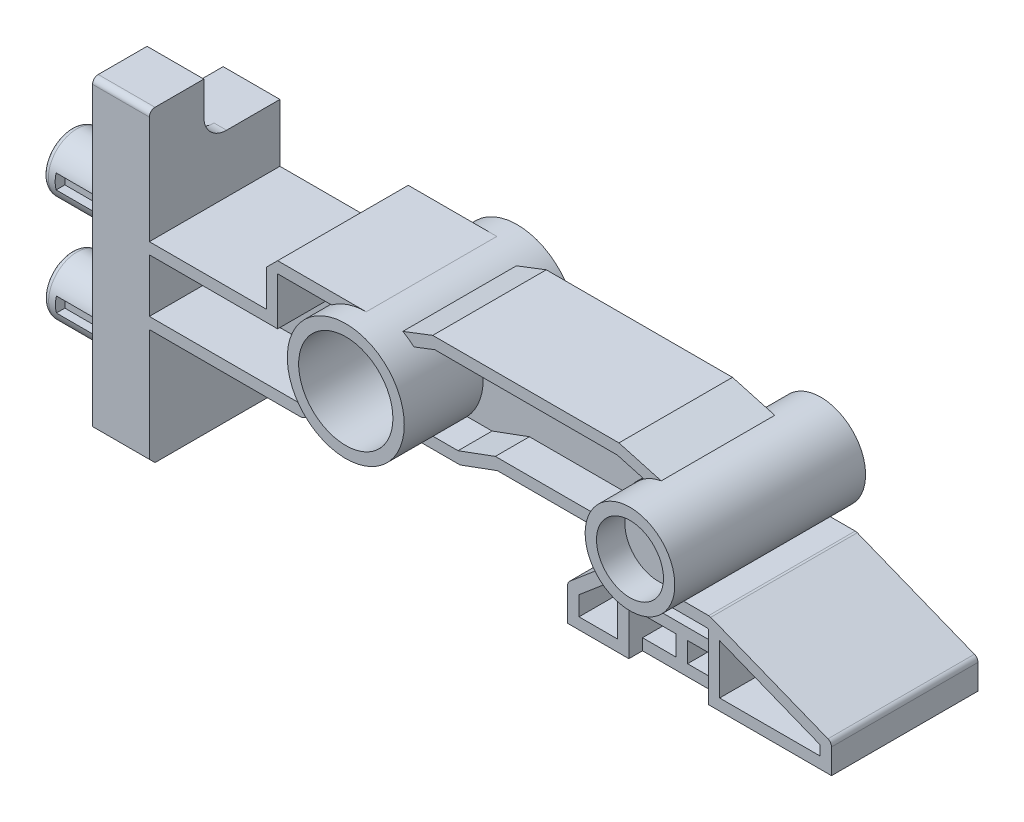
SolidWorks part; units mm, degrees
material "ABS"
ref_plane "Front Plane" through (0, 0, 0) normal (0, 0, 1) x (1, 0, 0)
ref_plane "Top Plane" through (0, 0, 0) normal (0, 1, 0) x (1, 0, 0)
ref_plane "Right Plane" through (0, 0, 0) normal (1, 0, 0) x (0, 0, -1)
sketch "Sketch1" plane through (0, 0, 0) normal (0, 0, 1) x (1, 0, 0)
  circle A0 centre (0, 0) radius 5.15
  circle A1 centre (0, 0) radius 4.15
  dimension "D1" = 10.3
  dimension "D2" = 1
extrude "Boss-Extrude1" add sketch "Sketch1" along normal blind 15.1
ref_plane "Plane1" through (0, 0, 1.8) normal (0, 0, -1) x (-1, 0, 0)
sketch "Sketch2" plane through (0, 0, 1.8) normal (0, 0, -1) x (-1, 0, 0)
  line L0 (0, 5.15) -> (8.8, 5.15)
  line L1 (8.8, 5.15) -> (8.8, 0.95)
  line L2 (8.8, 0.95) -> (19.1, 0.95)
  line L3 (2.7907, -4.3283) -> (5.6739, -5.7513)
  line L4 (5.6739, -5.7513) -> (19.1, -5.7513)
  line L6 (19.1, -5.7513) -> (19.1, -16.1513)
  line L7 (19.1, 0.95) -> (19.1, 10.95)
  line L8 (19.1, 10.95) -> (24.1, 10.95)
  line L9 (19.1, -16.1513) -> (24.1, -16.1513)
  line L10 (24.1, -16.1513) -> (24.1, 10.95)
  circle A0 centre (0, 0) radius 5.15 construction
  arc A1 (2.7907, -4.3283) -> (0, 5.15) centre (0, 0) ccw
  dimension "D1" = 8.8
  dimension "D2" = 4.2
  dimension "D3" = 10.3
  dimension "D4" = 10.4
  dimension "D5" = 10
  dimension "D6" = 5
extrude "Boss-Extrude2" add sketch "Sketch2" against normal blind 11.5
sketch "Sketch3" plane through (0, 0, 1.8) normal (0, 0, -1) x (-1, 0, 0)
  line L0 (-2.4711, 4.5184) -> (-5.1046, 5.5315)
  line L2 (-5.1046, 5.5315) -> (-21.5046, 5.5315)
  line L3 (-2.4138, -4.5493) -> (-6.1138, -4.5493)
  line L4 (-6.1138, -4.5493) -> (-9.3984, -3.3405)
  line L5 (-9.3984, -3.3405) -> (-21.5311, -3.3405)
  line L6 (-21.5046, 5.5315) -> (-25.2287, 4.4975)
  line L7 (-21.5311, -3.3405) -> (-25.9262, -3.3405)
  circle A0 centre (0, 0) radius 5.15 construction
  arc A1 (-25.9262, -3.3405) -> (-25.2287, 4.4975) centre (-25.9262, 0.6095) ccw
  arc A2 (-2.4711, 4.5184) -> (-2.4138, -4.5493) centre (0, 0) ccw
  dimension "D5" = 7.9
  dimension "D2" = 16.4
  dimension "D3" = 3.7
  dimension "D4" = 3.5
ref_plane "Plane2" through (0, 0, -0.8) normal (0, 0, -1) x (-1, 0, 0)
ref_plane "Plane3" through (0, 0, 2.55) normal (0, 0, -1) x (-1, 0, 0)
sketch "Sketch5" plane through (0, 0, 2.55) normal (0, 0, -1) x (-1, 0, 0)
  line L0 (-2.4711, 4.5184) -> (-5.1046, 5.5315)
  line L1 (-5.1046, 5.5315) -> (-21.5046, 5.5315)
  line L2 (-21.5046, 5.5315) -> (-25.2287, 4.4975)
  line L3 (-25.9262, -3.3405) -> (-21.5311, -3.3405)
  line L4 (-21.5311, -3.3405) -> (-9.3984, -3.3405)
  line L5 (-9.3984, -3.3405) -> (-6.1138, -4.5493)
  line L6 (-6.1138, -4.5493) -> (-2.4138, -4.5493)
  arc A0 (-2.4711, 4.5184) -> (-2.4138, -4.5493) centre (0, 0) ccw
  arc A1 (-25.9262, -3.3405) -> (-25.2287, 4.4975) centre (-25.9262, 0.6095) ccw
extrude "Boss-Extrude5" add sketch "Sketch5" against normal blind 10
sketch "Sketch6" plane through (0, 0, -0.8) normal (0, 0, -1) x (-1, 0, 0)
  circle A0 centre (-25.9262, 0.6095) radius 3.95
extrude "Boss-Extrude6" add sketch "Sketch6" against normal blind 16.8
sketch "Sketch7" plane through (-24.1, 0, 0) normal (-1, 0, 0) x (0, 0, 1)
  line L1 (13.3, 10.95) -> (1.8, 10.95) construction
  line L2 (8.5, 10.95) -> (8.5, 6.05)
  line L3 (8.5, 6.05) -> (1.8, 6.05)
  line L4 (1.8, -16.1513) -> (1.8, 10.95) construction
  line L5 (1.8, 6.05) -> (1.8, 10.95)
  line L6 (1.8, 10.95) -> (8.5, 10.95)
  dimension "D2" = 4.9
extrude "Cut-Extrude1" cut sketch "Sketch7" against normal blind 16.8
sketch "Sketch8" plane through (-24.1, 0, 0) normal (-1, 0, 0) x (0, 0, 1)
  line L0 (7.5573, -15.7) -> (7.6164, 7.3801) construction
  line L2 (13.3, -16.1513) -> (1.8, -16.1513) construction
  line L3 (1.8, 6.05) -> (8.5, 6.05) construction
  circle A1 centre (7.5687, -11.2513) radius 2.5
  circle A2 centre (7.5928, -1.85) radius 2.5
  dimension "D1" = 5
  dimension "D3" = 5
  dimension "D4" = 7.9
  dimension "D2" = 4.9
extrude "Boss-Extrude7" add sketch "Sketch8" along normal blind 7.6
sketch "Sketch9" plane through (0, 0, -0.8) normal (0, 0, -1) x (-1, 0, 0)
  circle A0 centre (-25.9262, 0.6095) radius 2.95
  circle A1 centre (-25.9262, 0.6095) radius 3.95 construction
  dimension "D1" = 1
extrude "Cut-Extrude2" cut sketch "Sketch9" against normal blind 13.4
sketch "Sketch10" plane through (0, 0, 16) normal (0, 0, 1) x (1, 0, 0)
  circle A0 centre (25.9262, 0.6095) radius 2.95
  circle A1 centre (25.9262, 0.6095) radius 3.95 construction
  dimension "D1" = 1
extrude "Cut-Extrude3" cut sketch "Sketch10" against normal blind 2.5
ref_plane "Plane5" through (0, 0, 1) normal (0, 0, -1) x (-1, 0, 0)
sketch "Sketch11" plane through (0, 0, 1) normal (0, 0, -1) x (-1, 0, 0)
  line L2 (-33.12, -3.243) -> (-41.5746, -6.6092)
  line L3 (-41.5746, -6.6092) -> (-41.5746, -9.1405)
  line L4 (-21.9682, -2.9208) -> (-18.3416, -5.9852)
  line L5 (-18.3416, -5.9852) -> (-18.3416, -9.1405)
  line L6 (-18.3416, -9.1405) -> (-41.5746, -9.1405)
  line L7 (-33.12, -3.243) -> (-30.8531, -2.3405)
  line L8 (-30.8531, -2.3405) -> (-28.553, -2.3405)
  line L9 (-21.9682, -2.9208) -> (-22.655, -2.3405)
  line L10 (-23.2994, -2.3405) -> (-22.655, -2.3405)
  line L11 (-25.9262, -3.3405) -> (-9.3984, -3.3405) construction
  arc A1 (-28.553, -2.3405) -> (-23.2994, -2.3405) centre (-25.9262, 0.6095) ccw
  dimension "D1" = 6.8
  dimension "D2" = 23.2329
  dimension "D3" = 1
extrude "Boss-Extrude14" add sketch "Sketch11" against normal blind 12.9
sketch "Sketch13" plane through (0, 0, 8.5) normal (0, 0, -1) x (-1, 0, 0)
  line L1 (20.2, 9.85) -> (23, 9.85)
  line L2 (20.2, 9.85) -> (20.2, 6.05)
  line L3 (20.2, 6.05) -> (23, 6.05)
  line L4 (23, 9.85) -> (23, 6.05)
  line L5 (19.1, 6.05) -> (24.1, 6.05) construction
  line L6 (19.1, 10.95) -> (24.1, 10.95) construction
  line L7 (19.1, 10.95) -> (19.1, 6.05) construction
  line L8 (24.1, 6.05) -> (24.1, 10.95) construction
  dimension "D1" = 1.1
  dimension "D2" = 1.1
  dimension "D3" = 1.1
extrude "Cut-Extrude4" cut sketch "Sketch13" against normal blind 3.6
sketch "Sketch14" plane through (0, 0, 1.8) normal (0, 0, -1) x (-1, 0, 0)
  line L0 (20.2, 6.05) -> (23, 6.05) construction
  line L1 (20.1, 5.05) -> (23.1, 5.05)
  line L2 (20.1, 5.05) -> (20.1, -1.55)
  line L3 (20.1, -1.55) -> (23.1, -1.55)
  line L4 (23.1, 5.05) -> (23.1, -1.55)
  line L5 (20.1, -2.55) -> (23.1, -2.55)
  line L6 (20.1, -2.55) -> (20.1, -10.65)
  line L7 (20.1, -10.65) -> (23.1, -10.65)
  line L8 (23.1, -2.55) -> (23.1, -10.65)
  line L9 (20.1, -11.65) -> (23.1, -11.65)
  line L10 (20.1, -11.65) -> (20.1, -15.1513)
  line L11 (20.1, -15.1513) -> (23.1, -15.1513)
  line L12 (23.1, -11.65) -> (23.1, -15.1513)
  line L13 (24.1, -16.1513) -> (24.1, 6.05) construction
  line L14 (21.6, 6.05) -> (21.6, -16.1513) construction
  line L15 (19.1, -16.1513) -> (24.1, -16.1513) construction
  line L18 (19.1, 6.05) -> (19.1, 0.95) construction
  point P18 (21.6, 5.05)
  dimension "D1" = 1
  dimension "D2" = 6.6
  dimension "D3" = 1
  dimension "D4" = 1
  dimension "D5" = 8.1
  dimension "D6" = 1
  dimension "D7" = 1
  dimension "D8" = 1
extrude "Cut-Extrude5" cut sketch "Sketch14" against normal blind 10.2
sketch "Sketch15" plane through (-24.1, 0, 0) normal (-1, 0, 0) x (0, 0, 1)
  line L0 (7.5928, -1.85) -> (7.5928, -11.2514) construction
  line L1 (10.0928, -1.85) -> (5.0928, -1.85) construction
  line L2 (4.7322, -1.2) -> (5.9454, -1.2)
  line L3 (4.7322, -1.2) -> (4.7322, -2.5)
  line L4 (4.7322, -2.5) -> (5.9454, -2.5)
  line L5 (5.9454, -1.2) -> (5.9454, -2.5)
  line L6 (10.4534, -2.5) -> (9.2402, -2.5)
  line L7 (9.2402, -1.2) -> (9.2402, -2.5)
  line L8 (10.4534, -1.2) -> (9.2402, -1.2)
  line L9 (10.4534, -1.2) -> (10.4534, -2.5)
  line L10 (4.7322, -6.55) -> (10.0928, -6.55) construction
  line L11 (10.4534, -11.9) -> (10.4534, -10.6)
  line L12 (10.4534, -11.9) -> (9.2402, -11.9)
  line L13 (9.2402, -11.9) -> (9.2402, -10.6)
  line L14 (10.4534, -10.6) -> (9.2402, -10.6)
  line L15 (4.7322, -10.6) -> (5.9454, -10.6)
  line L16 (5.9454, -11.9) -> (5.9454, -10.6)
  line L17 (4.7322, -11.9) -> (5.9454, -11.9)
  line L18 (4.7322, -11.9) -> (4.7322, -10.6)
  circle A2 centre (7.5928, -1.85) radius 2.5 construction
  circle A3 centre (7.5928, -1.85) radius 2.5 construction
  point P2 (5.9454, -1.85)
  dimension "D4" = 4.7
  dimension "D1" = 1.3
  dimension "D2" = 1.6474
  dimension "D3" = 0.65
extrude "Cut-Extrude6" cut sketch "Sketch15" along normal blind 6.5
ref_plane "Plane7" through (0, 0, 7.55) normal (0, 0, 1) x (1, 0, 0)
sketch "Sketch16" plane through (0, 0, 1.8) normal (0, 0, -1) x (-1, 0, 0)
  line L0 (7.8, 4.15) -> (7.8, -0.05)
  line L1 (7.8, -0.05) -> (19.1, -0.05)
  line L2 (19.1, -0.05) -> (19.1, -4.7513)
  line L3 (19.1, -4.7513) -> (7.5352, -4.7513)
  line L4 (7.5352, -4.7513) -> (5.9073, -4.7513)
  line L5 (5.9073, -4.7513) -> (3.6473, -3.6359)
  line L6 (7.8, 4.15) -> (3.0496, 4.15)
  line L7 (8.8, 5.15) -> (0, 5.15) construction
  line L8 (8.8, 0.95) -> (8.8, 5.15) construction
  line L9 (19.1, 0.95) -> (8.8, 0.95) construction
  line L10 (19.1, 6.05) -> (19.1, 0.95) construction
  line L11 (5.6739, -5.7513) -> (19.1, -5.7513) construction
  line L12 (2.7907, -4.3283) -> (5.6739, -5.7513) construction
  arc A0 (3.6473, -3.6359) -> (3.0496, 4.15) centre (0, 0) ccw
  dimension "D1" = 1
  dimension "D2" = 1
  dimension "D3" = 1
  dimension "D4" = 1
  dimension "D5" = 1
extrude "Cut-Extrude7" cut sketch "Sketch16" against normal blind 4.9
sketch "Sketch17" plane through (0, 0, 2.55) normal (0, 0, -1) x (-1, 0, 0)
  line L0 (-22.655, -2.3405) -> (-9.2203, -2.3405)
  line L1 (-9.2203, -2.3405) -> (-5.9356, -3.5493)
  line L2 (-5.9356, -3.5493) -> (-3.7316, -3.5493)
  line L3 (-3.4501, 3.8235) -> (-5.2903, 4.5315)
  line L4 (-5.2903, 4.5315) -> (-21.3684, 4.5315)
  line L5 (-21.3684, 4.5315) -> (-23.6642, 3.894)
  line L6 (-21.5046, 5.5315) -> (-25.2287, 4.4975) construction
  line L7 (-5.1046, 5.5315) -> (-21.5046, 5.5315) construction
  line L8 (-2.4711, 4.5184) -> (-5.1046, 5.5315) construction
  line L9 (-21.4715, -3.3405) -> (-9.3984, -3.3405) construction
  line L10 (-9.3984, -3.3405) -> (-6.1138, -4.5493) construction
  line L11 (-6.1138, -4.5493) -> (-2.4138, -4.5493) construction
  line L12 (-22.655, -2.3405) -> (-23.2425, -2.3405)
  arc A0 (-23.2425, -2.3405) -> (-23.6642, 3.894) centre (-25.9262, 0.6095) ccw
  arc A1 (-2.4711, 4.5184) -> (-2.4138, -4.5493) centre (0, 0) ccw construction
  arc A3 (-3.4501, 3.8235) -> (-3.7316, -3.5493) centre (0, 0) ccw
  dimension "D1" = 1
  dimension "D2" = 1
  dimension "D3" = 1
  dimension "D4" = 1
  dimension "D5" = 1
extrude "Cut-Extrude8" cut sketch "Sketch17" against normal blind 4.4
sketch "Sketch18" plane through (0, 0, 2.55) normal (0, 0, -1) x (-1, 0, 0)
  line L0 (-22.655, -2.3405) -> (-21.4715, -3.3405)
  line L1 (-21.4715, -3.3405) -> (-9.3984, -3.3405)
  line L2 (-9.3984, -3.3405) -> (-6.1138, -4.5493)
  line L3 (-6.1138, -4.5493) -> (-2.4138, -4.5493)
  line L4 (-22.655, -2.3405) -> (-9.2203, -2.3405)
  line L5 (-9.2203, -2.3405) -> (-5.9356, -3.5493)
  line L6 (-5.9356, -3.5493) -> (-3.7316, -3.5493)
  arc A0 (-2.4138, -4.5493) -> (-3.7316, -3.5493) centre (0, 0) cw
extrude "Cut-Extrude9" cut sketch "Sketch18" against normal blind 1.4
sketch "Sketch19" plane through (0, 0, 1) normal (0, 0, -1) x (-1, 0, 0)
  line L0 (-40.5746, -7.2874) -> (-40.5746, -8.1405)
  line L1 (-40.5746, -8.1405) -> (-19.3416, -8.1405)
  line L2 (-19.3416, -8.1405) -> (-19.3416, -6.4494)
  line L3 (-19.3416, -6.4494) -> (-23.0209, -3.3405)
  line L4 (-23.0209, -3.3405) -> (-30.6613, -3.3405)
  line L5 (-30.6613, -3.3405) -> (-40.5746, -7.2874)
  line L6 (-30.8531, -2.3405) -> (-41.5746, -6.6092) construction
  line L7 (-41.5746, -6.6092) -> (-41.5746, -9.1405) construction
  line L8 (-41.5746, -9.1405) -> (-18.3416, -9.1405) construction
  line L9 (-18.3416, -9.1405) -> (-18.3416, -5.9852) construction
  line L10 (-18.3416, -5.9852) -> (-22.655, -2.3405) construction
  line L11 (-28.553, -2.3405) -> (-30.8531, -2.3405) construction
  line L12 (-30.7229, -3.365) -> (-30.7229, -5.3669)
  line L13 (-30.7229, -8.1405) -> (-31.7229, -8.1405)
  line L14 (-31.7229, -8.1405) -> (-31.7229, -3.7631)
  line L15 (-31.7229, -3.7631) -> (-30.7229, -3.365)
  line L16 (-23.7295, -3.3405) -> (-23.7295, -5.3669)
  line L17 (-23.7295, -8.1405) -> (-22.7295, -8.1405)
  line L18 (-22.7295, -8.1405) -> (-22.7295, -3.5867)
  line L19 (-22.7295, -3.5867) -> (-23.0209, -3.3405)
  line L20 (-23.7295, -3.3405) -> (-23.0209, -3.3405)
  line L21 (-30.7229, -5.3669) -> (-23.7295, -5.3669)
  line L23 (-23.7295, -6.3669) -> (-26.6973, -6.3669)
  line L25 (-27.6973, -6.3669) -> (-27.6973, -8.1405)
  line L26 (-27.6973, -8.1405) -> (-26.6973, -8.1405)
  line L27 (-26.6973, -8.1405) -> (-26.6973, -6.3669)
  line L29 (-30.7229, -6.3669) -> (-30.7229, -8.1405)
  line L30 (-27.6973, -6.3669) -> (-30.7229, -6.3669)
  line L31 (-23.7295, -6.3669) -> (-23.7295, -8.1405)
  dimension "D1" = 1
  dimension "D2" = 1
  dimension "D3" = 1
  dimension "D4" = 1
  dimension "D5" = 1
  dimension "D6" = 1
  dimension "D7" = 1
  dimension "D8" = 1
  dimension "D9" = 1
  dimension "D10" = 1
extrude "Cut-Extrude10" cut sketch "Sketch19" against normal through all contours L1 L14 L5 L0 | L12 L21 L16 L4 L5 | L25 L30 L29 L1 | L31 L23 L27 L1 | L18 L1 L2 L3 region at (35.1547, -6.635, 1) region at (27.226, -4.3538, 1) region at (29.2101, -7.2537, 1) region at (25.2134, -7.2537, 1) region at (21.2944, -6.4699, 1)
mirror "Mirror1" about plane through (0, 0, 7.55) normal (0, 0, 1) of "Cut-Extrude7", "Cut-Extrude8", "Cut-Extrude9"
fillet "Fillet1" radius 2 2 edges at (-23.55, 6.05, 8.5) (-19.65, 6.05, 8.5)
fillet "Fillet2" radius 0.5 2 edges at (-31.7, -11.2513, 10.0687) (-31.7, -1.85, 10.0928)
chamfer "Chamfer1" distance 1 angle 45 1 edges at (-8.8, 5.15, 7.55)
fillet "Fillet3" radius 0.5 5 edges at (-21.6, 10.95, 13.3) (30.8531, -2.3405, 7.45) (22.655, -2.3405, 2.475) (18.3416, -5.9852, 7.45) (41.5746, -6.6092, 7.45)
chamfer "Chamfer2" distance 0.5 angle 45 2 edges at (-21.6, -16.1513, 1.8) (-21.6, -16.1513, 13.3)
sketch "Sketch20" plane through (0, 0, 1) normal (0, 0, -1) x (-1, 0, 0)
  line L0 (-30.7229, -5.3669) -> (-30.7229, -6.3669)
  line L1 (-30.7229, -6.3669) -> (-27.6973, -6.3669)
  line L2 (-27.6973, -6.3669) -> (-27.6973, -8.1405)
  line L3 (-27.6973, -8.1405) -> (-30.7229, -8.1405)
  line L4 (-30.7229, -8.1405) -> (-30.7229, -9.1405)
  line L5 (-41.5746, -9.1405) -> (-18.3416, -9.1405) construction
  line L6 (-30.7229, -9.1405) -> (-23.7295, -9.1405)
  line L10 (-23.7295, -3.3405) -> (-23.7295, -5.3669) construction
  line L11 (-30.7229, -5.3669) -> (-23.7295, -5.3669)
  line L12 (-23.7295, -6.3669) -> (-26.6973, -6.3669)
  line L13 (-26.6973, -6.3669) -> (-26.6973, -8.1405)
  line L14 (-23.7295, -6.3669) -> (-23.7295, -8.1405)
  line L15 (-23.7295, -8.1405) -> (-26.6973, -8.1405)
  line L16 (-23.7295, -5.3669) -> (-23.7295, -6.3669)
  line L17 (-23.7295, -8.1405) -> (-23.7295, -9.1405)
  line M10 (-41.5746, -9.1405) -> (-18.3416, -9.1405)
  line M19 (-23.7295, -5.3669) -> (-30.7229, -5.3669)
  line M24 (-30.7229, -6.3669) -> (-27.6973, -6.3669)
  line M25 (-27.6973, -6.3669) -> (-27.6973, -8.1405)
  line M26 (-27.6973, -8.1405) -> (-30.7229, -8.1405)
  line M28 (-26.6973, -6.3669) -> (-23.7295, -6.3669)
  line M30 (-23.7295, -8.1405) -> (-26.6973, -8.1405)
  line M31 (-26.6973, -8.1405) -> (-26.6973, -6.3669)
extrude "Cut-Extrude11" cut sketch "Sketch20" against normal blind 1.4 contours L17 L16 L0 L4 M30 M31 M28 M19 M24 M25 M26 M10 region at (27.223, -7.2537, 1)
mirror "Mirror2" about plane through (0, 0, 7.55) normal (0, 0, 1) of "Cut-Extrude11"
fillet "Fillet4" radius 0.5 1 edges at (-7.8, 4.15, 4.25)
